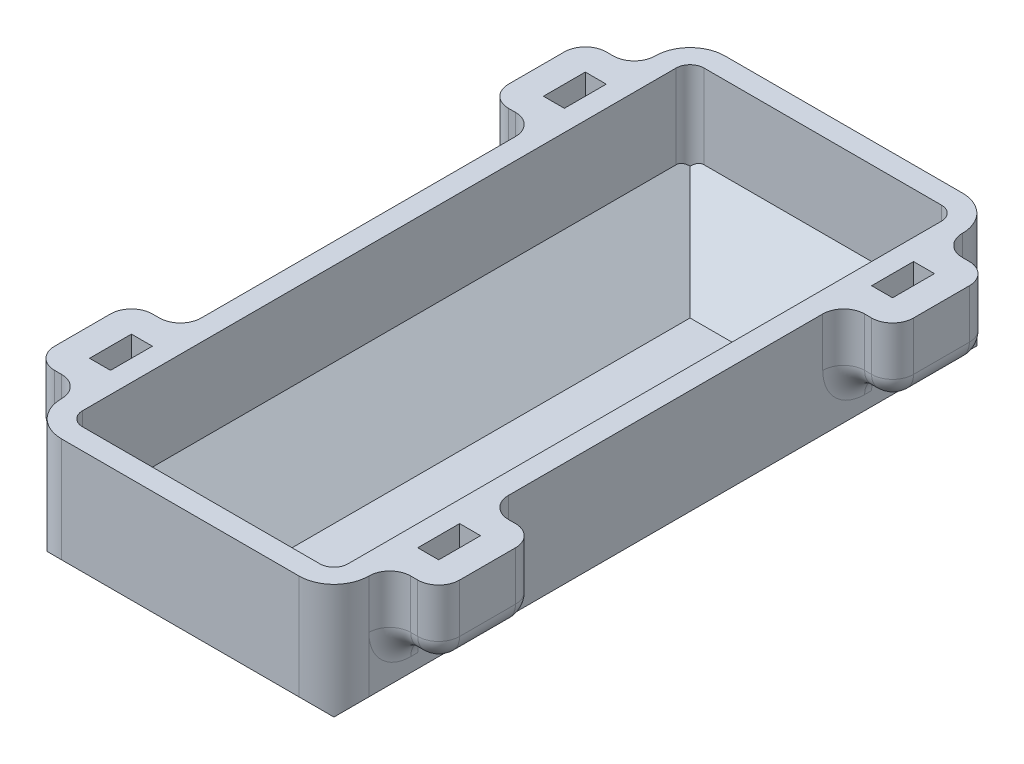
SolidWorks part; units mm, degrees
ref_plane "Front Plane" through (0, 0, 0) normal (0, 0, 1) x (1, 0, 0)
ref_plane "Top Plane" through (0, 0, 0) normal (0, 1, 0) x (1, 0, 0)
ref_plane "Right Plane" through (0, 0, 0) normal (1, 0, 0) x (0, 0, -1)
sketch "Sketch1" plane through (0, 0, 0) normal (0, 1, 0) x (1, 0, 0)
  line L1 (-22, -47.5) -> (22, -47.5)
  line L2 (-22, -47.5) -> (-22, 47.5)
  line L3 (-22, 47.5) -> (22, 47.5)
  line L4 (22, -47.5) -> (22, 47.5)
  line L5 (-22, -47.5) -> (22, 47.5) construction
  line L6 (-22, 47.5) -> (22, -47.5) construction
  point P0 (0, 0)
  dimension "D1" = 95
  dimension "D2" = 44
extrude "Boss-Extrude1" add sketch "Sketch1" along normal blind 25
sketch "Sketch2" plane through (0, 25, 0) normal (0, 1, 0) x (1, 0, 0)
  line L1 (19, -44.5) -> (-19, -44.5)
  line L2 (19, -44.5) -> (19, 44.5)
  line L3 (19, 44.5) -> (-19, 44.5)
  line L4 (-19, -44.5) -> (-19, 44.5)
  line L5 (19, -44.5) -> (-19, 44.5) construction
  line L6 (19, 44.5) -> (-19, -44.5) construction
  point P0 (0, 0)
  dimension "D1" = 89
  dimension "D2" = 38
extrude "Cut-Extrude1" cut sketch "Sketch2" against normal blind 22
chamfer "Chamfer1" distance 10 angle 45 8 edges at (0, 0, -47.5) (-22, 0, 0) (0, 0, 47.5) (22, 0, 0) (0, 3, -44.5) (19, 3, 0) (0, 3, 44.5) (-19, 3, 0)
fillet "Fillet1" radius 2 4 edges at (-19, 19, 44.5) (19, 19, 44.5) (19, 19, -44.5) (-19, 19, -44.5)
fillet "Fillet2" radius 5 4 edges at (22, 17.5, -47.5) (22, 17.5, 47.5) (-22, 17.5, 47.5) (-22, 17.5, -47.5)
sketch "Sketch3" plane through (22, 0, 0) normal (1, 0, 0) x (0, 0, -1)
  line L0 (-42.5, 25) -> (42.5, 25) construction
  line L1 (-25.5, 15) -> (-39.5, 15)
  line L2 (-25.5, 15) -> (-25.5, 25)
  line L3 (-25.5, 25) -> (-39.5, 25)
  line L4 (-39.5, 15) -> (-39.5, 25)
  line L5 (-25.5, 15) -> (-39.5, 25) construction
  line L6 (-25.5, 25) -> (-39.5, 15) construction
  line L7 (-42.5, 25) -> (-42.5, 10) construction
  line L8 (0, 25) -> (0, 10) construction
  line L9 (-29.5, 17.8571) -> (-35.5, 17.8571) construction
  line L10 (-29.5, 17.8571) -> (-29.5, 22.1429) construction
  line L11 (-29.5, 22.1429) -> (-35.5, 22.1429) construction
  line L12 (-35.5, 17.8571) -> (-35.5, 22.1429) construction
  line L13 (-29.5, 17.8571) -> (-35.5, 22.1429) construction
  line L14 (-29.5, 22.1429) -> (-35.5, 17.8571) construction
  line L15 (-42.5, 10) -> (42.5, 10) construction
  line L16 (25.5, 25) -> (39.5, 25)
  line L17 (29.5, 22.1429) -> (35.5, 17.8571) construction
  line L18 (29.5, 17.8571) -> (35.5, 22.1429) construction
  line L19 (35.5, 17.8571) -> (35.5, 22.1429) construction
  line L20 (29.5, 22.1429) -> (35.5, 22.1429) construction
  line L21 (29.5, 17.8571) -> (29.5, 22.1429) construction
  line L22 (29.5, 17.8571) -> (35.5, 17.8571) construction
  line L23 (25.5, 25) -> (39.5, 15) construction
  line L24 (25.5, 15) -> (39.5, 25) construction
  line L25 (39.5, 15) -> (39.5, 25)
  line L26 (25.5, 15) -> (25.5, 25)
  line L27 (25.5, 15) -> (39.5, 15)
  point P0 (-32.5, 20)
  point P9 (-32.5, 20)
  point P26 (32.5, 20)
  dimension "D1" = 3
  dimension "D2" = 14
  dimension "D3" = 10
  dimension "D4" = 6
extrude "Boss-Extrude2" add sketch "Sketch3" along normal blind 7
sketch "Sketch5" plane through (-22, 0, 0) normal (-1, 0, 0) x (0, 0, 1)
  line L0 (-42.5, 25) -> (42.5, 25) construction
  line L1 (25.5, 15) -> (39.5, 15)
  line L2 (25.5, 15) -> (25.5, 25)
  line L3 (25.5, 25) -> (39.5, 25)
  line L4 (39.5, 15) -> (39.5, 25)
  line L5 (25.5, 15) -> (39.5, 25) construction
  line L6 (25.5, 25) -> (39.5, 15) construction
  line L7 (42.5, 10) -> (42.5, 25) construction
  line L8 (0, 25) -> (0, 10) construction
  line L9 (-42.5, 10) -> (42.5, 10) construction
  line L10 (-39.5, 15) -> (-39.5, 25)
  line L11 (-25.5, 25) -> (-39.5, 15) construction
  line L12 (-25.5, 15) -> (-39.5, 25) construction
  line L13 (-25.5, 25) -> (-39.5, 25)
  line L14 (-25.5, 15) -> (-25.5, 25)
  line L15 (-25.5, 15) -> (-39.5, 15)
  point P0 (32.5, 20)
  point P17 (-32.5, 20)
  dimension "D1" = 10
  dimension "D2" = 14
  dimension "D3" = 3
extrude "Boss-Extrude3" add sketch "Sketch5" along normal blind 7
fillet "Fillet3" radius 3 32 edges at (29, 20, 25.5) (29, 15, 32.5) (29, 20, 39.5) (29, 20, -25.5) (29, 15, -32.5) (29, 20, -39.5) (-29, 20, 39.5) (-29, 15, 32.5) (-29, 20, 25.5) (-29, 20, -25.5) (-29, 15, -32.5) (-29, 20, -39.5) (25.5, 15, 25.5) (25.5, 15, 39.5) (25.5, 15, -25.5) (25.5, 15, -39.5) (-25.5, 15, 39.5) (-25.5, 15, 25.5) (-25.5, 15, -25.5) (-25.5, 15, -39.5) (-22, 20, -39.5) (22, 20, 39.5) (22, 20, 25.5) (22, 20, -25.5) (22, 20, -39.5) (-22, 20, 25.5) (-22, 20, 39.5) (-22, 15, -32.5) (22, 15, 32.5) (22, 15, -32.5) (-22, 15, 32.5) (-22, 20, -25.5)
sketch "Sketch7" plane through (0, 25, 0) normal (0, 1, 0) x (1, 0, 0)
  line L0 (-26, 39.5) -> (-25, 39.5) construction
  line L13 (-25, 35.5) -> (-22, 35.5)
  line L14 (-25, 35.5) -> (-25, 29.5)
  line L15 (-25, 29.5) -> (-22, 29.5)
  line L16 (-22, 35.5) -> (-22, 29.5)
  line L17 (0, 47.5) -> (0, -19.4636) construction
  line L18 (17, 47.5) -> (-17, 47.5) construction
  line L19 (-22, 0) -> (22, 0) construction
  line L20 (-22, 22.5) -> (-22, -22.5) construction
  line L21 (22, -22.5) -> (22, 22.5) construction
  line L22 (22, 35.5) -> (22, 29.5)
  line L23 (25, 29.5) -> (22, 29.5)
  line L24 (25, 35.5) -> (25, 29.5)
  line L25 (25, 35.5) -> (22, 35.5)
  line L26 (25, -35.5) -> (22, -35.5)
  line L27 (25, -35.5) -> (25, -29.5)
  line L28 (25, -29.5) -> (22, -29.5)
  line L29 (22, -35.5) -> (22, -29.5)
  line L30 (-22, -35.5) -> (-22, -29.5)
  line L31 (-25, -29.5) -> (-22, -29.5)
  line L32 (-25, -35.5) -> (-25, -29.5)
  line L33 (-25, -35.5) -> (-22, -35.5)
  dimension "D1" = 4
  dimension "D2" = 3
  dimension "D3" = 6
extrude "Cut-Extrude2" cut sketch "Sketch7" against normal through all and the other way through all
